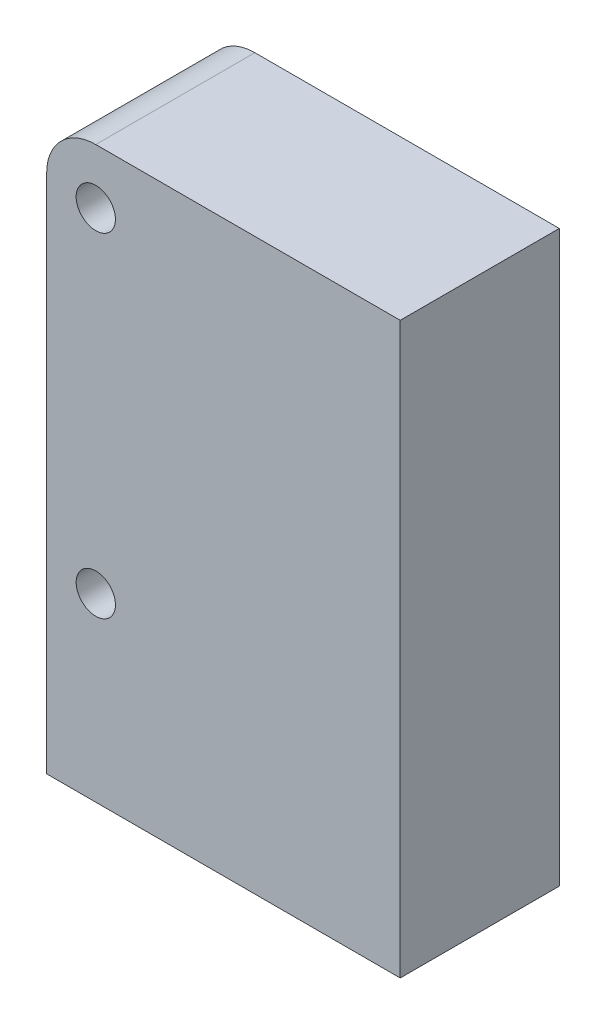
SolidWorks part; units mm, degrees
ref_plane "Plan de face" through (0, 0, 0) normal (0, 0, 1) x (1, 0, 0)
ref_plane "Plan de dessus" through (0, 0, 0) normal (0, 1, 0) x (1, 0, 0)
ref_plane "Plan de droite" through (0, 0, 0) normal (1, 0, 0) x (0, 0, -1)
sketch "Esquisse1" plane through (0, 0, 0) normal (0, 0, 1) x (1, 0, 0)
  line L1 (0, 0) -> (18, 0)
  line L2 (0, 0) -> (0, 29)
  line L3 (0, 29) -> (18, 29)
  line L4 (18, 0) -> (18, 29)
  dimension "D1" = 18
  dimension "D2" = 29
extrude "Boss.-Extru.1" add sketch "Esquisse1" along normal blind 8.1
sketch "Esquisse3" plane through (0, 0, 8.1) normal (0, 0, 1) x (1, 0, 0)
  line L0 (0, 29) -> (0, 0) construction
  line L3 (2.5, 9.2) -> (2.5, 26.2) construction
  line L4 (2.5, 26.2) -> (10.1767, 26.2) construction
  line L5 (0, 0) -> (18, 0) construction
  circle A2 centre (2.5, 26.2) radius 1
  circle A4 centre (2.5, 9.2) radius 1
  dimension "D1" = 2.5
  dimension "D5" = 17
  dimension "D3" = 2
  dimension "D2" = 9.2
extrude "Enlèv. mat.-Extru.1" cut sketch "Esquisse3" against normal through all
fillet "Congé1" radius 2.5 1 edges at (0, 29, 4.05)
